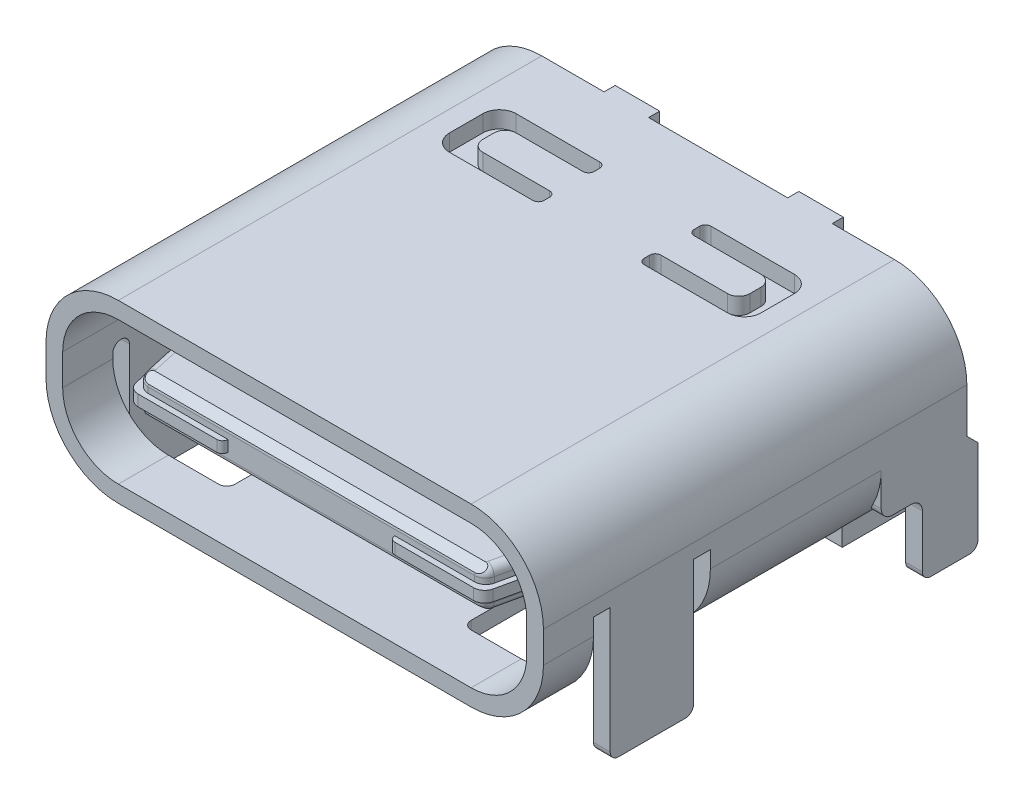
SolidWorks part; units mm, degrees
ref_plane "Płaszczyzna przednia" through (0, 0, 0) normal (0, 0, 1) x (1, 0, 0)
ref_plane "Płaszczyzna górna" through (0, 0, 0) normal (0, 1, 0) x (1, 0, 0)
ref_plane "Płaszczyzna prawa" through (0, 0, 0) normal (1, 0, 0) x (0, 0, -1)
sketch "Sketch1" plane through (0, 0, 0) normal (0, 0, 1) x (1, 0, 0)
  line L0 (-4.47, 0.28) -> (-4.47, -0.28)
  line L1 (-3.17, -1.58) -> (3.17, -1.58)
  line L2 (4.47, -0.28) -> (4.47, 0.28)
  line L3 (3.17, 1.58) -> (-3.17, 1.58)
  arc A0 (-4.47, -0.28) -> (-3.17, -1.58) centre (-3.17, -0.28) ccw
  arc A1 (3.17, -1.58) -> (4.47, -0.28) centre (3.17, -0.28) ccw
  arc A2 (4.47, 0.28) -> (3.17, 1.58) centre (3.17, 0.28) ccw
  arc A3 (-3.17, 1.58) -> (-4.47, 0.28) centre (-3.17, 0.28) ccw
extrude "Boss-Extrude1" add sketch "Sketch1" along normal blind 7.61
sketch "Sketch2" plane through (0, 0, 7.61) normal (0, 0, 1) x (1, 0, 0)
  line L4 (3.17, 1.28) -> (-3.17, 1.28)
  line L5 (-4.17, 0.28) -> (-4.17, -0.28)
  line L6 (-3.17, -1.28) -> (3.17, -1.28)
  line L7 (4.17, -0.28) -> (4.17, 0.28)
  line L8 (-4.47, 0.28) -> (-4.47, -0.28)
  line L9 (-3.17, -1.58) -> (3.17, -1.58)
  line L10 (4.47, -0.28) -> (4.47, 0.28)
  line L11 (3.17, 1.58) -> (-3.17, 1.58)
  line L12 (-4.47, 0.28) -> (-4.47, -0.28)
  line L13 (-3.17, -1.58) -> (3.17, -1.58)
  line L14 (4.47, -0.28) -> (4.47, 0.28)
  line L15 (3.17, 1.58) -> (-3.17, 1.58)
  arc A4 (-3.17, 1.28) -> (-4.17, 0.28) centre (-3.17, 0.28) ccw
  arc A5 (-4.17, -0.28) -> (-3.17, -1.28) centre (-3.17, -0.28) ccw
  arc A6 (3.17, -1.28) -> (4.17, -0.28) centre (3.17, -0.28) ccw
  arc A7 (4.17, 0.28) -> (3.17, 1.28) centre (3.17, 0.28) ccw
  arc A8 (-3.17, 1.58) -> (-4.47, 0.28) centre (-3.17, 0.28) ccw
  arc A9 (-4.47, -0.28) -> (-3.17, -1.58) centre (-3.17, -0.28) ccw
  arc A10 (3.17, -1.58) -> (4.47, -0.28) centre (3.17, -0.28) ccw
  arc A11 (4.47, 0.28) -> (3.17, 1.58) centre (3.17, 0.28) ccw
  arc A12 (-3.17, 1.58) -> (-4.47, 0.28) centre (-3.17, 0.28) ccw
  arc A13 (-4.47, -0.28) -> (-3.17, -1.58) centre (-3.17, -0.28) ccw
  arc A14 (3.17, -1.58) -> (4.47, -0.28) centre (3.17, -0.28) ccw
  arc A15 (4.47, 0.28) -> (3.17, 1.58) centre (3.17, 0.28) ccw
  dimension "D1" = 0
  dimension "D2" = 0.3
extrude "Cut-Extrude1" cut sketch "Sketch2" against normal blind 4.7 flip side to cut
sketch "Sketch3" plane through (0, 1.58, 0) normal (0, 1, 0) x (1, 0, 0)
  line L0 (1.25, 0) -> (-1.25, 0)
  line L1 (0.9, -2.13) -> (0.9, -2.23)
  line L2 (1, -2.33) -> (2.5, -2.33)
  line L3 (2.8, -2.03) -> (2.8, -1.43)
  line L4 (2.5, -1.13) -> (1, -1.13)
  line L5 (0.9, -1.23) -> (0.9, -1.33)
  line L6 (1, -1.43) -> (2.2, -1.43)
  line L7 (2.4, -1.63) -> (2.4, -1.83)
  line L8 (2.2, -2.03) -> (1, -2.03)
  line L9 (-2.8, -1.43) -> (-2.8, -2.03)
  line L10 (-2.5, -2.33) -> (-1, -2.33)
  line L11 (-0.9, -2.23) -> (-0.9, -2.13)
  line L12 (-1, -2.03) -> (-2.2, -2.03)
  line L13 (-2.4, -1.83) -> (-2.4, -1.63)
  line L14 (-2.2, -1.43) -> (-1, -1.43)
  line L15 (-0.9, -1.33) -> (-0.9, -1.23)
  line L16 (-1, -1.13) -> (-2.5, -1.13)
  line L17 (0, 0) -> (0, 0.4904) construction
  arc A0 (0.9, -2.23) -> (1, -2.33) centre (1, -2.23) ccw
  arc A1 (2.5, -2.33) -> (2.8, -2.03) centre (2.5, -2.03) ccw
  arc A2 (2.8, -1.43) -> (2.5, -1.13) centre (2.5, -1.43) ccw
  arc A3 (1, -1.13) -> (0.9, -1.23) centre (1, -1.23) ccw
  arc A4 (0.9, -1.33) -> (1, -1.43) centre (1, -1.33) ccw
  arc A5 (2.4, -1.63) -> (2.2, -1.43) centre (2.2, -1.63) ccw
  arc A6 (2.2, -2.03) -> (2.4, -1.83) centre (2.2, -1.83) ccw
  arc A7 (1, -2.03) -> (0.9, -2.13) centre (1, -2.13) ccw
  arc A8 (-2.5, -1.13) -> (-2.8, -1.43) centre (-2.5, -1.43) ccw
  arc A9 (-2.8, -2.03) -> (-2.5, -2.33) centre (-2.5, -2.03) ccw
  arc A10 (-1, -2.33) -> (-0.9, -2.23) centre (-1, -2.23) ccw
  arc A11 (-0.9, -2.13) -> (-1, -2.03) centre (-1, -2.13) ccw
  arc A12 (-2.4, -1.83) -> (-2.2, -2.03) centre (-2.2, -1.83) ccw
  arc A13 (-2.2, -1.43) -> (-2.4, -1.63) centre (-2.2, -1.63) ccw
  arc A14 (-1, -1.43) -> (-0.9, -1.33) centre (-1, -1.33) ccw
  arc A15 (-0.9, -1.23) -> (-1, -1.13) centre (-1, -1.23) ccw
extrude "Cut-Extrude2" cut sketch "Sketch3" against normal blind 0.3 contours L15 A15 L16 A8 L9 A9 L10 A10 L11 A11 L12 A12 L13 A13 L14 A14 | L4 A3 L5 A4 L6 A5 L7 A6 L8 A7 L1 A0 L2 A1 L3 A2 region at (-2.6962, 1.58, 1.2338)
sketch "Sketch4" plane through (0, 0, 0) normal (0, 0, -1) x (-1, 0, 0)
  line L0 (0, 0.98) -> (0, 1.58) construction
  line L1 (-3.97, 0.48) -> (-3.97, -0.42)
  line L2 (-3.67, -0.72) -> (3.67, -0.72)
  line L3 (3.97, -0.42) -> (3.97, 0.48)
  line L4 (3.47, 0.98) -> (2.05, 0.98)
  line L5 (2.05, 0.98) -> (2.05, 1.58)
  line L6 (2.05, 1.58) -> (1.25, 1.58)
  line L7 (1.25, 1.58) -> (1.25, 0.98)
  line L8 (1.25, 0.98) -> (-1.25, 0.98)
  line L9 (-1.25, 0.98) -> (-1.25, 1.58)
  line L10 (-1.25, 1.58) -> (-2.05, 1.58)
  line L11 (-2.05, 1.58) -> (-2.05, 0.98)
  line L12 (-2.05, 0.98) -> (-3.47, 0.98)
  arc A0 (-3.97, -0.42) -> (-3.67, -0.72) centre (-3.67, -0.42) ccw
  arc A1 (3.67, -0.72) -> (3.97, -0.42) centre (3.67, -0.42) ccw
  arc A2 (3.97, 0.48) -> (3.47, 0.98) centre (3.47, 0.48) ccw
  arc A3 (-3.47, 0.98) -> (-3.97, 0.48) centre (-3.47, 0.48) ccw
extrude "Boss-Extrude2" add sketch "Sketch4" along normal blind 0.2
sketch "Sketch5" plane through (4.47, 0, 0) normal (1, 0, 0) x (0, 0, -1)
  line L0 (-6.41, -0.2) -> (-6.41, -2.23)
  line L1 (-6.26, -2.38) -> (-5.06, -2.38)
  line L2 (-4.91, -2.23) -> (-4.91, -0.2)
  line L3 (-4.61, -0.2) -> (-4.61, -0.28)
  line L4 (-4.61, -0.28) -> (-1.54, -0.28)
  line L5 (-1.54, -0.28) -> (-1.54, -0.88)
  line L6 (-1.34, -1.08) -> (-1, -1.08)
  line L7 (-0.8, -1.28) -> (-0.8, -2.23)
  line L8 (-0.65, -2.38) -> (0.05, -2.38)
  line L9 (0.2, -2.23) -> (0.2, -0.72)
  line L10 (0.2, -0.72) -> (0, -0.52)
  line L11 (0, -0.52) -> (0, 0.28)
  line L12 (-7.61, 0.28) -> (-7.61, -0.28)
  line L13 (-7.61, -0.28) -> (-6.71, -0.28)
  line L14 (-6.71, -0.28) -> (-6.71, -0.2)
  line L15 (-7.61, 0.2097) -> (-7.61, 0.28)
  line L16 (0, 0.28) -> (0, 0.2097)
  line L17 (0, 0.2097) -> (-7.61, 0.2097)
  arc A0 (-6.41, -2.23) -> (-6.26, -2.38) centre (-6.26, -2.23) ccw
  arc A1 (-5.06, -2.38) -> (-4.91, -2.23) centre (-5.06, -2.23) ccw
  arc A2 (-4.61, -0.2) -> (-4.91, -0.2) centre (-4.76, -0.2) ccw
  arc A3 (-1.54, -0.88) -> (-1.34, -1.08) centre (-1.34, -0.88) ccw
  arc A4 (-0.8, -1.28) -> (-1, -1.08) centre (-1, -1.28) ccw
  arc A5 (-0.8, -2.23) -> (-0.65, -2.38) centre (-0.65, -2.23) ccw
  arc A6 (0.05, -2.38) -> (0.2, -2.23) centre (0.05, -2.23) ccw
  arc A7 (-6.41, -0.2) -> (-6.71, -0.2) centre (-6.56, -0.2) ccw
  point P34 (-7.61, 1.58)
  line M2 (-7.61, -0.28) -> (0, -0.28)
  line M3 (0, -0.28) -> (0, 0.28)
extrude "Boss-Extrude3" add sketch "Sketch5" against normal blind 0.3 contours L1 A1 L2 L0 A0 M2 | A7 L0 L2 A2 L3 L17 L12 L14 M2 M3 | L8 A6 L9 L10 L11 L5 A3 L6 A4 L7 A5 M2 region at (4.47, -0.0305, 3.744) region at (4.47, -1.3269, 5.66) region at (4.47, -1.2021, 0.5055)
sketch "Sketch6" plane through (0, -1.58, 0) normal (0, -1, 0) x (1, 0, 0)
  line L0 (4.47, 4.61) -> (3.17, 4.61)
  line L1 (2.27, 4.61) -> (3.17, 4.61)
  line L2 (2.12, 4.76) -> (2.12, 6.56)
  line L3 (2.27, 6.71) -> (3.17, 6.71)
  line L4 (3.17, 6.71) -> (4.47, 6.71)
  line L5 (-3.17, 4.61) -> (-4.47, 4.61)
  line L6 (-3.17, 4.61) -> (-2.27, 4.61)
  line L7 (-3.17, 6.71) -> (-2.27, 6.71)
  line L8 (-2.12, 6.56) -> (-2.12, 4.76)
  line L9 (-4.47, 6.71) -> (-3.17, 6.71)
  line L10 (-2.12, 5.66) -> (2.12, 5.66) construction
  line L11 (0, 5.66) -> (0, 7.61) construction
  line L12 (-4.47, 6.71) -> (-4.47, 4.61)
  line L13 (4.47, 6.71) -> (4.47, 6.41)
  line L14 (-3.17, 7.61) -> (3.17, 7.61) construction
  line L15 (4.47, 6.41) -> (4.17, 6.41)
  line L16 (4.47, 6.41) -> (4.17, 6.41) construction
  line L17 (4.17, 6.41) -> (4.17, 4.91)
  line L18 (4.17, 4.91) -> (4.47, 4.91)
  line L19 (4.47, 4.91) -> (4.47, 4.61)
  arc A0 (2.12, 4.76) -> (2.27, 4.61) centre (2.27, 4.76) ccw
  arc A1 (2.27, 6.71) -> (2.12, 6.56) centre (2.27, 6.56) ccw
  arc A2 (-2.27, 4.61) -> (-2.12, 4.76) centre (-2.27, 4.76) ccw
  arc A3 (-2.12, 6.56) -> (-2.27, 6.71) centre (-2.27, 6.56) ccw
  point P24 (0, 7.61)
extrude "Cut-Extrude3" cut sketch "Sketch6" against normal blind 1.6
sketch "Sketch7" plane through (0, -1.58, 0) normal (0, -1, 0) x (1, 0, 0)
  line L0 (0, 0) -> (0, -1.7425) construction
  line L1 (4.17, 0) -> (4.17, 1.94)
  line L2 (-4.17, 0) -> (-4.17, 1.94)
  line L3 (-4.17, 1.94) -> (4.17, 1.94)
  line L4 (-4.17, 0) -> (4.17, 0)
extrude "Cut-Extrude4" cut sketch "Sketch7" against normal blind 0.15
sketch "Sketch8" plane through (0, 0, 0) normal (0, 0, -1) x (-1, 0, 0)
  line L0 (0, -1.58) -> (0, -2.8477) construction
  line L1 (-3.17, -1.58) -> (3.17, -1.58) construction
  line L2 (-3.7762, -1.43) -> (-4.17, -1.43)
  line L3 (-4.17, -2.23) -> (-4.17, -0.72) construction
  line L4 (-4.17, -1.43) -> (-4.17, -1.1107)
  line L5 (4.17, -1.43) -> (4.17, -1.1107)
  line L6 (3.7762, -1.43) -> (4.17, -1.43)
  arc A0 (-4.17, -1.1107) -> (-3.7762, -1.43) centre (-3.17, -0.28) ccw construction
  arc A1 (-4.17, -1.1107) -> (-3.7762, -1.43) centre (-3.17, -0.28) ccw
  arc A2 (4.17, -1.1107) -> (3.7762, -1.43) centre (3.17, -0.28) cw
extrude "Boss-Extrude4" add sketch "Sketch8" against normal up to surface (1.94 mm away) up to face at (0, -1.5235, 1.94)
ref_plane "Plane1" through (0, 0, 0) normal (-1, 0, 0) x (0, 0, 1)
mirror "Mirror1" about plane through (0, 0, 0) normal (-1, 0, 0) of "Boss-Extrude3"
sketch "Sketch9" plane through (0, -1.43, 0) normal (0, -1, 0) x (1, 0, 0)
  line L0 (0, 1.94) -> (0, -0.2) construction
  line L1 (-0.6, 0.05) -> (-0.6, -0.29)
  line L2 (-0.6, -0.29) -> (-0.4, -0.29)
  line L3 (-0.4, -0.29) -> (-0.4, 0.05)
  line L4 (-0.4, 0.05) -> (-0.4, 0.2)
  line L5 (-0.4, 0.2) -> (-0.6, 0.2)
  line L6 (-0.6, 0.2) -> (-0.6, 0.05)
  line L7 (-0.9, 0.05) -> (-0.9, 0.2)
  line L8 (-0.9, 0.2) -> (-1.1, 0.2)
  line L9 (-1.1, 0.2) -> (-1.1, 0.05)
  line L10 (-1.1, 0.05) -> (-1.1, -0.29)
  line L11 (-1.1, -0.29) -> (-0.9, -0.29)
  line L12 (-0.9, -0.29) -> (-0.9, 0.05)
  line L13 (-1.6, 0.05) -> (-1.6, -0.29)
  line L14 (-1.6, -0.29) -> (-1.4, -0.29)
  line L15 (-1.4, -0.29) -> (-1.4, 0.05)
  line L16 (-1.4, 0.05) -> (-1.4, 0.2)
  line L17 (-1.4, 0.2) -> (-1.6, 0.2)
  line L18 (-1.6, 0.2) -> (-1.6, 0.05)
  line L19 (-1.9, 0.05) -> (-1.9, 0.2)
  line L20 (-1.9, 0.2) -> (-2.1, 0.2)
  line L21 (-2.1, 0.2) -> (-2.1, 0.05)
  line L22 (-2.1, 0.05) -> (-2.1, -0.29)
  line L23 (-2.1, -0.29) -> (-1.9, -0.29)
  line L24 (-1.9, -0.29) -> (-1.9, 0.05)
  line L25 (-2.6, 0.05) -> (-2.6, -0.29)
  line L26 (-2.6, -0.29) -> (-2.4, -0.29)
  line L27 (-2.4, -0.29) -> (-2.4, 0.05)
  line L28 (-2.4, 0.05) -> (-2.4, 0.2)
  line L29 (-2.4, 0.2) -> (-2.6, 0.2)
  line L30 (-2.6, 0.2) -> (-2.6, 0.05)
  line L31 (-2.9, 0.05) -> (-2.9, 0.2)
  line L32 (-2.9, 0.2) -> (-3.1, 0.2)
  line L33 (-3.1, 0.2) -> (-3.1, 0.05)
  line L34 (-3.1, 0.05) -> (-3.1, -0.29)
  line L35 (-3.1, -0.29) -> (-2.9, -0.29)
  line L36 (-2.9, -0.29) -> (-2.9, 0.05)
  line L37 (0.6, 0.05) -> (0.6, 0.2)
  line L38 (0.6, 0.2) -> (0.4, 0.2)
  line L39 (0.4, 0.2) -> (0.4, 0.05)
  line L40 (0.4, 0.05) -> (0.4, -0.29)
  line L41 (0.4, -0.29) -> (0.6, -0.29)
  line L42 (0.6, -0.29) -> (0.6, 0.05)
  line L43 (0.9, 0.05) -> (0.9, -0.29)
  line L44 (0.9, -0.29) -> (1.1, -0.29)
  line L45 (1.1, -0.29) -> (1.1, 0.05)
  line L46 (1.1, 0.05) -> (1.1, 0.2)
  line L47 (1.1, 0.2) -> (0.9, 0.2)
  line L48 (0.9, 0.2) -> (0.9, 0.05)
  line L49 (1.6, 0.05) -> (1.6, 0.2)
  line L50 (1.6, 0.2) -> (1.4, 0.2)
  line L51 (1.4, 0.2) -> (1.4, 0.05)
  line L52 (1.4, 0.05) -> (1.4, -0.29)
  line L53 (1.4, -0.29) -> (1.6, -0.29)
  line L54 (1.6, -0.29) -> (1.6, 0.05)
  line L55 (1.9, 0.05) -> (1.9, -0.29)
  line L56 (1.9, -0.29) -> (2.1, -0.29)
  line L57 (2.1, -0.29) -> (2.1, 0.05)
  line L58 (2.1, 0.05) -> (2.1, 0.2)
  line L59 (2.1, 0.2) -> (1.9, 0.2)
  line L60 (1.9, 0.2) -> (1.9, 0.05)
  line L61 (2.6, 0.05) -> (2.6, 0.2)
  line L62 (2.6, 0.2) -> (2.4, 0.2)
  line L63 (2.4, 0.2) -> (2.4, 0.05)
  line L64 (2.4, 0.05) -> (2.4, -0.29)
  line L65 (2.4, -0.29) -> (2.6, -0.29)
  line L66 (2.6, -0.29) -> (2.6, 0.05)
  line L67 (2.9, 0.05) -> (2.9, -0.29)
  line L68 (2.9, -0.29) -> (3.1, -0.29)
  line L69 (3.1, -0.29) -> (3.1, 0.05)
  line L70 (3.1, 0.05) -> (3.1, 0.2)
  line L71 (3.1, 0.2) -> (2.9, 0.2)
  line L72 (2.9, 0.2) -> (2.9, 0.05)
  line L73 (2.65, 1.31) -> (2.65, 1.01)
  line L74 (2.65, 1.01) -> (2.85, 1.01)
  line L75 (2.85, 1.01) -> (2.85, 1.31)
  line L76 (2.85, 1.31) -> (2.85, 1.46)
  line L77 (2.85, 1.46) -> (2.65, 1.46)
  line L78 (2.65, 1.46) -> (2.65, 1.31)
  line L79 (3.45, 1.31) -> (3.45, 1.46)
  line L80 (3.45, 1.46) -> (3.15, 1.46)
  line L81 (3.15, 1.46) -> (3.15, 1.31)
  line L82 (3.15, 1.31) -> (3.15, 1.01)
  line L83 (3.15, 1.01) -> (3.45, 1.01)
  line L84 (3.45, 1.01) -> (3.45, 1.31)
  line L85 (2.15, 1.31) -> (2.15, 1.01)
  line L86 (2.15, 1.01) -> (2.35, 1.01)
  line L87 (2.35, 1.01) -> (2.35, 1.31)
  line L88 (2.35, 1.31) -> (2.35, 1.46)
  line L89 (2.35, 1.46) -> (2.15, 1.46)
  line L90 (2.15, 1.46) -> (2.15, 1.31)
  line L91 (1.85, 1.31) -> (1.85, 1.46)
  line L92 (1.85, 1.46) -> (1.65, 1.46)
  line L93 (1.65, 1.46) -> (1.65, 1.31)
  line L94 (1.65, 1.31) -> (1.65, 1.01)
  line L95 (1.65, 1.01) -> (1.85, 1.01)
  line L96 (1.85, 1.01) -> (1.85, 1.31)
  line L97 (1.15, 1.31) -> (1.15, 1.01)
  line L98 (1.15, 1.01) -> (1.35, 1.01)
  line L99 (1.35, 1.01) -> (1.35, 1.31)
  line L100 (1.35, 1.31) -> (1.35, 1.46)
  line L101 (1.35, 1.46) -> (1.15, 1.46)
  line L102 (1.15, 1.46) -> (1.15, 1.31)
  line L103 (0.85, 1.31) -> (0.85, 1.46)
  line L104 (0.85, 1.46) -> (0.65, 1.46)
  line L105 (0.65, 1.46) -> (0.65, 1.31)
  line L106 (0.65, 1.31) -> (0.65, 1.01)
  line L107 (0.65, 1.01) -> (0.85, 1.01)
  line L108 (0.85, 1.01) -> (0.85, 1.31)
  line L109 (0.15, 1.31) -> (0.15, 1.01)
  line L110 (0.15, 1.01) -> (0.35, 1.01)
  line L111 (0.35, 1.01) -> (0.35, 1.31)
  line L112 (0.35, 1.31) -> (0.35, 1.46)
  line L113 (0.35, 1.46) -> (0.15, 1.46)
  line L114 (0.15, 1.46) -> (0.15, 1.31)
  line L115 (-0.15, 1.31) -> (-0.15, 1.46)
  line L116 (-0.15, 1.46) -> (-0.35, 1.46)
  line L117 (-0.35, 1.46) -> (-0.35, 1.31)
  line L118 (-0.35, 1.31) -> (-0.35, 1.01)
  line L119 (-0.35, 1.01) -> (-0.15, 1.01)
  line L120 (-0.15, 1.01) -> (-0.15, 1.31)
  line L121 (-0.85, 1.31) -> (-0.85, 1.01)
  line L122 (-0.85, 1.01) -> (-0.65, 1.01)
  line L123 (-0.65, 1.01) -> (-0.65, 1.31)
  line L124 (-0.65, 1.31) -> (-0.65, 1.46)
  line L125 (-0.65, 1.46) -> (-0.85, 1.46)
  line L126 (-0.85, 1.46) -> (-0.85, 1.31)
  line L127 (-1.15, 1.31) -> (-1.15, 1.46)
  line L128 (-1.15, 1.46) -> (-1.35, 1.46)
  line L129 (-1.35, 1.46) -> (-1.35, 1.31)
  line L130 (-1.35, 1.31) -> (-1.35, 1.01)
  line L131 (-1.35, 1.01) -> (-1.15, 1.01)
  line L132 (-1.15, 1.01) -> (-1.15, 1.31)
  line L133 (-1.85, 1.31) -> (-1.85, 1.01)
  line L134 (-1.85, 1.01) -> (-1.65, 1.01)
  line L135 (-1.65, 1.01) -> (-1.65, 1.31)
  line L136 (-1.65, 1.31) -> (-1.65, 1.46)
  line L137 (-1.65, 1.46) -> (-1.85, 1.46)
  line L138 (-1.85, 1.46) -> (-1.85, 1.31)
  line L139 (-2.15, 1.31) -> (-2.15, 1.46)
  line L140 (-2.15, 1.46) -> (-2.35, 1.46)
  line L141 (-2.35, 1.46) -> (-2.35, 1.31)
  line L142 (-2.35, 1.31) -> (-2.35, 1.01)
  line L143 (-2.35, 1.01) -> (-2.15, 1.01)
  line L144 (-2.15, 1.01) -> (-2.15, 1.31)
  line L145 (-2.85, 1.31) -> (-2.85, 1.01)
  line L146 (-2.85, 1.01) -> (-2.65, 1.01)
  line L147 (-2.65, 1.01) -> (-2.65, 1.31)
  line L148 (-2.65, 1.31) -> (-2.65, 1.46)
  line L149 (-2.65, 1.46) -> (-2.85, 1.46)
  line L150 (-2.85, 1.46) -> (-2.85, 1.31)
  line L151 (-3.15, 1.31) -> (-3.15, 1.46)
  line L152 (-3.15, 1.46) -> (-3.45, 1.46)
  line L153 (-3.45, 1.46) -> (-3.45, 1.31)
  line L154 (-3.45, 1.31) -> (-3.45, 1.01)
  line L155 (-3.45, 1.01) -> (-3.15, 1.01)
  line L156 (-3.15, 1.01) -> (-3.15, 1.31)
  line L157 (3.67, -0.2) -> (-3.67, -0.2) construction
  point P158 (0, -0.2)
extrude "Boss-Extrude5" add sketch "Sketch9" along normal blind 0.2 separate body
sketch "Sketch10" plane through (-3.1, 0, 0) normal (-1, 0, 0) x (0, 0, 1)
  line L0 (1.01, -1.63) -> (1.3171, -1.63)
  line L1 (1.46, -1.63) -> (1.01, -1.63) construction
  line L2 (1.46, -1.43) -> (1.46, -1.4871)
  line L3 (1.46, -1.63) -> (1.46, -1.43) construction
  line L4 (1.01, -1.63) -> (1.5187, -1.7895)
  line L5 (1.5187, -1.7895) -> (1.579, -1.532)
  line L6 (1.579, -1.532) -> (1.46, -1.43)
  line L7 (-0.29, -1.63) -> (0.1, -1.63)
  line L8 (0.2, -1.63) -> (-0.29, -1.63) construction
  line L9 (0.2, -1.43) -> (0.2, -1.53)
  line L10 (0.2, -1.63) -> (0.2, -1.43) construction
  line L11 (0.2, -1.43) -> (0.4482, -1.7765)
  line L12 (0.4482, -1.7765) -> (0.0399, -1.8068)
  line L13 (0.0399, -1.8068) -> (-0.29, -1.63)
  arc A0 (1.3171, -1.63) -> (1.46, -1.4871) centre (1.3171, -1.4871) ccw
  arc A1 (0.2, -1.53) -> (0.1, -1.63) centre (0.1, -1.53) cw
extrude "Cut-Extrude5" cut sketch "Sketch10" against normal up to surface (6.55 mm away) and the other way up to surface (0.35 mm away) up to face at (3.45, -1.53, 1.235) other way up to face at (-3.45, -1.53, 1.235)
sketch "Sketch11" plane through (-3.1, 0, 0) normal (-1, 0, 0) x (0, 0, 1)
  line L0 (-0.29, -1.63) -> (0.1, -1.63) construction
  line L1 (0.2, -1.43) -> (0.2, -1.53) construction
  line L2 (0.2, -1.43) -> (0.4482, -1.7765) construction
  line L3 (0.4482, -1.7765) -> (0.0399, -1.8068) construction
  line L4 (0.0399, -1.8068) -> (-0.29, -1.63) construction
  line L5 (-0.29, -1.63) -> (0.1, -1.63)
  line L6 (0.2, -1.43) -> (0.2, -1.53)
  line L7 (0.2, -1.43) -> (0.4482, -1.7765)
  line L8 (0.4482, -1.7765) -> (0.0399, -1.8068)
  line L9 (0.0399, -1.8068) -> (-0.29, -1.63)
  arc A0 (0.1, -1.63) -> (0.2, -1.53) centre (0.1, -1.53) ccw construction
  arc A1 (0.1, -1.63) -> (0.2, -1.53) centre (0.1, -1.53) ccw
extrude "Cut-Extrude6" cut sketch "Sketch11" against normal up to surface (6.2 mm away) up to face at (3.1, -1.53, -0.045)
sketch "Sketch12" plane through (0, 0, 2.91) normal (0, 0, 1) x (1, 0, 0)
  line L0 (0, 0.5) -> (0, 1.58) construction
  line L1 (-3.165, 0.2) -> (-3.165, -0.2)
  line L2 (-2.865, -0.5) -> (2.865, -0.5)
  line L3 (3.165, -0.2) -> (3.165, 0.2)
  line L4 (2.865, 0.5) -> (-2.865, 0.5)
  line L5 (3.17, 1.58) -> (-3.17, 1.58) construction
  arc A0 (-3.165, -0.2) -> (-2.865, -0.5) centre (-2.865, -0.2) ccw
  arc A1 (2.865, -0.5) -> (3.165, -0.2) centre (2.865, -0.2) ccw
  arc A2 (3.165, 0.2) -> (2.865, 0.5) centre (2.865, 0.2) ccw
  arc A3 (-2.865, 0.5) -> (-3.165, 0.2) centre (-2.865, 0.2) ccw
  point P14 (0, 1.58)
extrude "Boss-Extrude6" add sketch "Sketch12" along normal blind 1.62 separate body
ref_plane "Plane2" through (0, 0, 0) normal (0, 1, 0) x (1, 0, 0)
sketch "Sketch13" plane through (0, 0, 0) normal (0, 1, 0) x (1, 0, 0)
  line L0 (3.045, -6.06) -> (3.045, -4.53)
  line L1 (3.205, -6.23) -> (3.085, -6.14)
  line L2 (3.245, -6.61) -> (3.245, -6.31)
  line L3 (3.1297, -7.1532) -> (3.2403, -6.6532)
  line L4 (-2.9344, -7.31) -> (2.9344, -7.31)
  line L5 (-3.2403, -6.6532) -> (-3.1297, -7.1532)
  line L6 (-3.245, -6.31) -> (-3.245, -6.61)
  line L7 (-3.085, -6.14) -> (-3.205, -6.23)
  line L8 (-3.045, -4.53) -> (-3.045, -6.06)
  line L9 (-3.045, -4.53) -> (3.045, -4.53)
  line L10 (2.865, -4.53) -> (-2.865, -4.53) construction
  arc A0 (3.045, -6.06) -> (3.085, -6.14) centre (3.145, -6.06) ccw
  arc A1 (3.2344, -6.2653) -> (3.205, -6.23) centre (3.145, -6.31) ccw
  arc A2 (3.245, -6.31) -> (3.2344, -6.2653) centre (3.145, -6.31) ccw
  arc A3 (3.2403, -6.6532) -> (3.245, -6.61) centre (3.045, -6.61) ccw
  arc A4 (3.0667, -7.26) -> (3.1297, -7.1532) centre (2.9344, -7.11) ccw
  arc A5 (2.9344, -7.31) -> (3.0667, -7.26) centre (2.9344, -7.11) ccw
  arc A6 (-3.0667, -7.26) -> (-2.9344, -7.31) centre (-2.9344, -7.11) ccw
  arc A7 (-3.1297, -7.1532) -> (-3.0667, -7.26) centre (-2.9344, -7.11) ccw
  arc A8 (-3.245, -6.61) -> (-3.2403, -6.6532) centre (-3.045, -6.61) ccw
  arc A9 (-3.205, -6.23) -> (-3.245, -6.31) centre (-3.145, -6.31) ccw
  arc A10 (-3.085, -6.14) -> (-3.045, -6.06) centre (-3.145, -6.06) ccw
  point P29 (0, -4.53)
extrude "Boss-Extrude7" add sketch "Sketch13" along normal mid plane 0.7
sketch "Sketch14" plane through (0, 0, 0) normal (0, 1, 0) x (1, 0, 0)
  line L0 (-3.205, -6.23) -> (-3.085, -6.14)
  line L1 (-3.045, -6.06) -> (-3.045, -4.53)
  line L2 (-3.045, -4.53) -> (-3.0911, -4.53)
  line L3 (-3.0911, -4.53) -> (-3.0911, -5.9695)
  line L4 (-3.1311, -6.0495) -> (-3.305, -6.18)
  line L5 (-3.345, -6.26) -> (-3.345, -6.6209)
  line L6 (-3.3403, -6.6641) -> (-3.21, -7.2532)
  line L7 (-3.0147, -7.41) -> (-1.6, -7.41)
  line L8 (-1.5, -7.31) -> (-2.9344, -7.31)
  line L9 (-3.1297, -7.1532) -> (-3.2403, -6.6532)
  line L10 (-3.245, -6.61) -> (-3.245, -6.31)
  line L11 (3.305, -6.18) -> (3.1311, -6.0495)
  line L12 (3.0911, -5.9695) -> (3.0911, -4.53)
  line L13 (3.0911, -4.53) -> (3.045, -4.53)
  line L14 (3.045, -4.53) -> (3.045, -6.06)
  line L15 (3.085, -6.14) -> (3.205, -6.23)
  line L16 (3.245, -6.31) -> (3.245, -6.61)
  line L17 (3.2403, -6.6532) -> (3.1297, -7.1532)
  line L18 (2.9344, -7.31) -> (1.5, -7.31)
  line L19 (1.6, -7.41) -> (3.0147, -7.41)
  line L20 (3.21, -7.2532) -> (3.3403, -6.6641)
  line L21 (3.345, -6.6209) -> (3.345, -6.26)
  arc A0 (-3.085, -6.14) -> (-3.045, -6.06) centre (-3.145, -6.06) ccw
  arc A1 (-3.1311, -6.0495) -> (-3.0911, -5.9695) centre (-3.1911, -5.9695) ccw
  arc A2 (-3.305, -6.18) -> (-3.345, -6.26) centre (-3.245, -6.26) ccw
  arc A3 (-3.345, -6.6209) -> (-3.3403, -6.6641) centre (-3.145, -6.6209) ccw
  arc A4 (-3.21, -7.2532) -> (-3.0147, -7.41) centre (-3.0147, -7.21) ccw
  arc A5 (-1.6, -7.41) -> (-1.5, -7.31) centre (-1.6, -7.31) ccw
  arc A6 (-3.1297, -7.1532) -> (-2.9344, -7.31) centre (-2.9344, -7.11) ccw
  arc A7 (-3.245, -6.61) -> (-3.2403, -6.6532) centre (-3.045, -6.61) ccw
  arc A8 (-3.205, -6.23) -> (-3.245, -6.31) centre (-3.145, -6.31) ccw
  arc A9 (3.0911, -5.9695) -> (3.1311, -6.0495) centre (3.1911, -5.9695) ccw
  arc A10 (3.045, -6.06) -> (3.085, -6.14) centre (3.145, -6.06) ccw
  arc A11 (3.245, -6.31) -> (3.205, -6.23) centre (3.145, -6.31) ccw
  arc A12 (3.2403, -6.6532) -> (3.245, -6.61) centre (3.045, -6.61) ccw
  arc A13 (2.9344, -7.31) -> (3.1297, -7.1532) centre (2.9344, -7.11) ccw
  arc A14 (1.5, -7.31) -> (1.6, -7.41) centre (1.6, -7.31) ccw
  arc A15 (3.0147, -7.41) -> (3.21, -7.2532) centre (3.0147, -7.21) ccw
  arc A16 (3.3403, -6.6641) -> (3.345, -6.6209) centre (3.145, -6.6209) ccw
  arc A17 (3.345, -6.26) -> (3.305, -6.18) centre (3.245, -6.26) ccw
  point P58 (3.045, -4.53)
extrude "Boss-Extrude8" add sketch "Sketch14" along normal mid plane 0.2 separate body
fillet "Fillet2" radius 0.15 34 edges at (3.045, -0.35, 5.295) (3.0556, -0.35, 6.1047) (3.145, -0.35, 6.185) (3.2344, -0.35, 6.2653) (3.245, -0.35, 6.46) (3.2438, -0.35, 6.6317) (3.185, -0.35, 6.9032) (3.0596, -0.35, 7.2659) (0, -0.35, 7.31) (-3.0596, -0.35, 7.2659) (-3.185, -0.35, 6.9032) (-3.2438, -0.35, 6.6317) (-3.245, -0.35, 6.46) (-3.2344, -0.35, 6.2653) (-3.145, -0.35, 6.185) (-3.0556, -0.35, 6.1047) (3.045, 0.35, 5.295) (3.0556, 0.35, 6.1047) (3.145, 0.35, 6.185) (3.2344, 0.35, 6.2653) (3.245, 0.35, 6.46) (3.2438, 0.35, 6.6317) (3.185, 0.35, 6.9032) (3.0596, 0.35, 7.2659) (0, 0.35, 7.31) (-3.0596, 0.35, 7.2659) (-3.185, 0.35, 6.9032) (-3.2438, 0.35, 6.6317) (-3.245, 0.35, 6.46) (-3.2344, 0.35, 6.2653) (-3.145, 0.35, 6.185) (-3.0556, 0.35, 6.1047) (-3.045, -0.35, 5.295) (-3.045, 0.35, 5.295)
sketch "Sketch15" plane through (4.4921, 0, 0.9936) normal (0.9764, 0, 0.216) x (0.216, 0, -0.9764)
  line L0 (-6.4957, 0.2182) -> (-6.2723, 0.3733)
  line L1 (-6.2723, 0.3733) -> (-6.5237, 0.3733)
  line L2 (-6.5237, 0.3733) -> (-6.4957, 0.2182)
  line L3 (-6.5735, 0) -> (-7.2149, 0) construction
  line L4 (-6.5237, -0.3733) -> (-6.4957, -0.2182)
  line L5 (-6.2723, -0.3733) -> (-6.5237, -0.3733)
  line L6 (-6.4957, -0.2182) -> (-6.2723, -0.3733)
sketch "Sketch16" plane through (4.47, 0, 0) normal (1, 0, 0) x (0, 0, -1)
  line L0 (-7.3633, -0.3733) -> (-7.3361, -0.2182) construction
  line L1 (-7.3361, -0.2182) -> (-7.1179, -0.3733) construction
  line L2 (-7.1179, -0.3733) -> (-7.3633, -0.3733) construction
  line L3 (-7.3633, 0.3733) -> (-7.3361, 0.2182) construction
  line L4 (-7.3361, 0.2182) -> (-7.1179, 0.3733) construction
  line L5 (-7.1179, 0.3733) -> (-7.3633, 0.3733) construction
  line L6 (-7.3633, -0.3733) -> (-7.3361, -0.2182)
  line L7 (-7.3361, -0.2182) -> (-7.1179, -0.3733)
  line L8 (-7.1179, -0.3733) -> (-7.3633, -0.3733)
  line L9 (-7.3633, 0.3733) -> (-7.3361, 0.2182)
  line L10 (-7.3361, 0.2182) -> (-7.1179, 0.3733)
  line L11 (-7.1179, 0.3733) -> (-7.3633, 0.3733)
extrude "Cut-Extrude10" cut sketch "Sketch16" against normal through all
